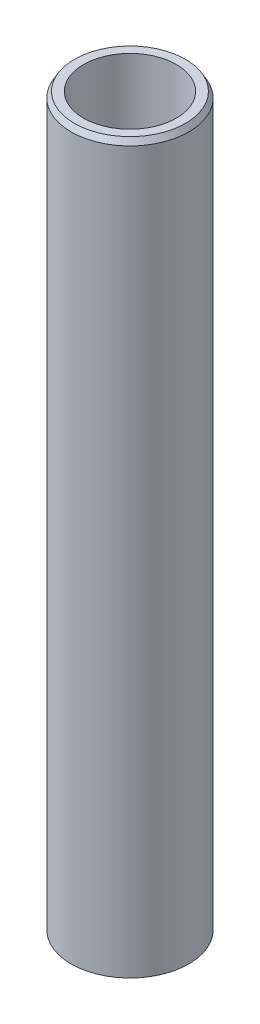
SolidWorks part; units mm, degrees
ref_plane "Front Plane" through (0, 0, 0) normal (0, 0, 1) x (1, 0, 0)
ref_plane "Top Plane" through (0, 0, 0) normal (0, 1, 0) x (1, 0, 0)
ref_plane "Right Plane" through (0, 0, 0) normal (1, 0, 0) x (0, 0, -1)
sketch "Sketch1" plane through (0, 0, 0) normal (0, 1, 0) x (1, 0, 0)
  circle A0 centre (0, 0) radius 32.5
  dimension "SHAFT_OD" = 65
extrude "Boss-Extrude1" add sketch "Sketch1" along normal blind 403.0289
sketch "Sketch2" plane through (0, 0, 0) normal (0, 1, 0) x (1, 0, 0)
  circle A0 centre (0, 0) radius 25.6667
  dimension "BORE_D" = 51.3333
extrude "Cut-Extrude1" cut sketch "Sketch2" along normal through all
chamfer "Chamfer1" distance 3.1757 angle 30 2 edges at (0, 403.0289, 32.5) (0, 0, 32.5) first distance on face at (0, 403.0289, 32.5) first distance on face at (0, 0, 25.6667)
